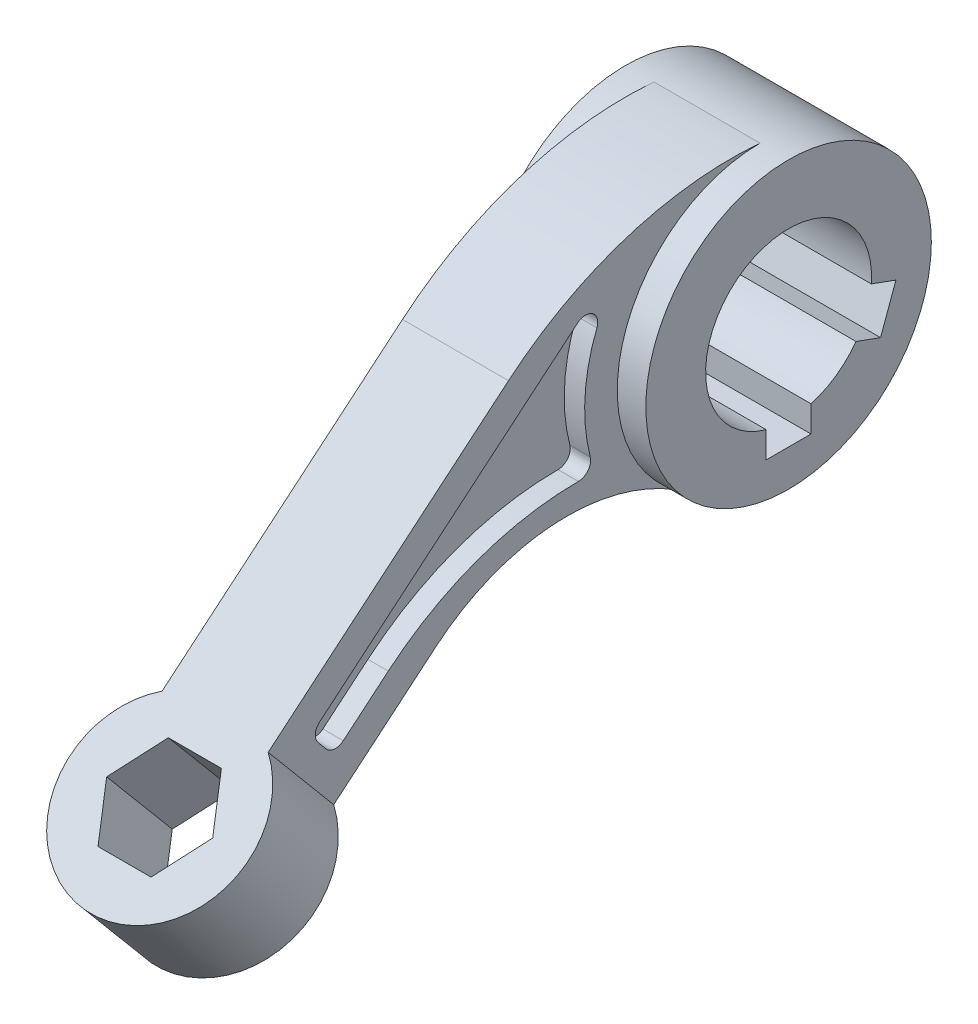
SolidWorks part; units mm, degrees
material "구리"
ref_plane "정면" through (0, 0, 0) normal (0, 0, 1) x (1, 0, 0)
ref_plane "윗면" through (0, 0, 0) normal (0, 1, 0) x (1, 0, 0)
ref_plane "우측면" through (0, 0, 0) normal (1, 0, 0) x (0, 0, -1)
sketch "Sketch1" plane through (0, 0, 0) normal (1, 0, 0) x (0, 0, -1)
  line L0 (0, 2.5639) -> (0, -54.5639) construction
  line L1 (22.5509, -14.0608) -> (16.5175, -11.8648)
  line L2 (-5.5, -26) -> (5.5, -26)
  line L3 (-5.5, -26) -> (-5.5, -19.5794)
  line L5 (5.5, -26) -> (5.5, -19.5794)
  line L6 (22.5509, -14.0608) -> (26.3131, -3.7242)
  line L7 (26.3131, -3.7242) -> (20.2797, -1.5282)
  line L9 (-61.6651, 15.4048) -> (-134.1818, -45.4439)
  line L10 (-134.1818, -45.4439) -> (-118.1121, -64.595)
  line L11 (-118.1121, -64.595) -> (-79.5317, -32.2222)
  line L12 (53.4671, 35) -> (-107.5928, 35) construction
  line L13 (-44.6559, 19.234) -> (-107.9587, -33.8834)
  line L14 (-108.3284, -38.1099) -> (-106.4001, -40.408)
  line L15 (-102.1736, -40.7778) -> (-91.1413, -31.5206)
  circle A0 centre (0, 0) radius 35
  arc A1 (5.5, -19.5794) -> (16.5175, -11.8648) centre (0, 0) ccw
  arc A2 (20.2797, -1.5282) -> (-5.5, -19.5794) centre (0, 0) ccw
  arc A3 (-61.6651, 15.4048) -> (0, 35) centre (-7.0281, -49.7089) cw
  arc A4 (-79.5317, -32.2222) -> (-20.4496, -28.4045) centre (-47.3923, -70.5244) cw
  arc A5 (-44.6559, 19.234) -> (-41.9077, 19.7514) centre (-42.7902, 16.8815) cw
  arc A6 (-91.1413, -31.5206) -> (-44.5255, -14.5531) centre (-44.5236, -87.0775) cw
  arc A7 (-39.9988, 15.7828) -> (-41.6217, -10.7997) centre (0, 0) ccw
  arc A8 (-41.9077, 19.7514) -> (-39.9988, 15.7828) centre (-42.7894, 16.8839) cw
  circle A10 centre (0, 0) radius 43 construction
  arc A11 (-41.6217, -10.7997) -> (-44.5255, -14.5531) centre (-44.5256, -11.5531) cw
  arc A13 (-108.3284, -38.1099) -> (-107.9587, -33.8834) centre (-106.0303, -36.1815) cw
  arc A14 (-106.4001, -40.408) -> (-102.1736, -40.7778) centre (-104.1019, -38.4796) ccw
  point P10 (0, -26)
  point P18 (0, 0)
  point P27 (-77.3476, -32.9486)
  point P28 (-18.8777, -29.4726)
  point P29 (-72.5951, -35.2385)
  point P32 (-17.1176, -30.5285)
  point P47 (-55.7741, 15.1214)
  point P48 (-55.5991, 15.1192)
  point P49 (-77.3351, -33.6863)
  point P50 (-76.8381, -33.996)
  point P51 (-56.5477, 15.1353)
  point P52 (0, 0)
  point P53 (0, 0)
  point P54 (-25.3958, -24.0843)
  point P55 (-20.0803, -28.8655)
  point P56 (0, 0)
  point P57 (0, 0)
  point P58 (-56.5002, 15.1342)
  point P59 (-56.2237, 15.1286)
  point P60 (0, 0)
  point P61 (0, 0)
  point P62 (-76.1089, -35.3273)
  point P63 (-74.944, -23.6864)
  point P64 (-47.1735, 19.4204)
  point P65 (-42.3042, -7.7043)
  point P66 (0, 0)
  point P67 (-41.6995, -9.5962)
  point P68 (-58.1212, 10.0015)
  point P69 (-53.0013, 12.3908)
  point P70 (-52.148, 12.3908)
  point P71 (0, 0)
  point P72 (-53.78, 13.7275)
  point P73 (-44.8926, 18.2271)
  point P74 (-45.1452, 16.2681)
  point P75 (-47.3347, 15.2705)
  point P76 (-46.1151, 14.3784)
  point P77 (-46.4038, 15.2444)
  point P78 (-102.1244, -36.128)
  point P79 (0, 0)
  point P80 (-44.6502, -14.0608)
  point P81 (-41.1655, -12.3445)
  point P82 (-44.8286, -13.315)
  point P83 (-48.6463, 12.4997)
  point P84 (-46.7209, 11.9654)
  point P85 (-62.2818, 16.3995)
  point P86 (0, 0)
  point P87 (-40.699, 10.6159)
  point P88 (-41.6079, -11.1231)
  point P89 (-73.3179, -34.9335)
  point P90 (-19.5792, -29.0113)
  point P91 (-60.2686, 15.0325)
  point P92 (-23.1853, -26)
  point P93 (0, 0)
  point P94 (-44.3341, -15.2674)
  point P95 (-41.1562, -10.5605)
  point P96 (-46.8563, 15.815)
  point P97 (0, 0)
  point P98 (-58.0521, 15.2005)
  point P99 (-41.9563, 9.4166)
  point P100 (-61.6651, 15.7828)
  point P101 (-44.6504, -14.0608)
  point P102 (0, 0)
  point P103 (0, 0)
  point P104 (-20.4496, -28.4045)
  point P105 (0, 0)
  point P106 (0, 0)
  point P107 (-44.5256, -14.5531)
  dimension "D1" = 70
  dimension "D5" = 85
  dimension "D7" = 50
  dimension "D12" = 3
  dimension "D14" = 8
  dimension "D15" = 3
  dimension "D16" = 3
  dimension "D17" = 3
  dimension "D2" = 26
  dimension "D3" = 11
  dimension "D6" = 25
  dimension "D8" = 40
  dimension "D9" = 132
  dimension "D13" = 8
  dimension "D11" = 8
  dimension "D4" = 2
extrude "Boss-Extrude2" add sketch "Sketch1" along normal mid plane 26 contours L11 A4 A0 A3 L9 L10 A14 L14 A13 L13 A5 A8 A7 A11 A6 L15 region at (0, 29.7052, 32.2634)
extrude "Boss-Extrude3" add sketch "Sketch1<4>" along normal mid plane 40 contours A3 A0 A2 L7 L6 L1 A1 L5 L2 L3 region at (0, 24.0487, -24.0487)
sketch "Sketch1<4>" plane through (0, 0, 0) normal (1, 0, 0) x (0, 0, -1) same geometry as "Sketch1"
extrude "Boss-Extrude4" add sketch "Sketch1<5>" along normal mid plane 16 contours L14 A14 L15 A6 A11 A7 A8 A5 L13 A13 region at (0, -10.3925, 67.4893)
sketch "Sketch1<5>" plane through (0, 0, 0) normal (1, 0, 0) x (0, 0, -1) same geometry as "Sketch1"
ref_plane "Plane1" through (0, 29.8285, 25.0291) normal (0, -0.766, -0.6428) x (-1, 0, 0)
sketch "Sketch2" plane through (0, 29.8285, 25.0291) normal (0, -0.766, -0.6428) x (-1, 0, 0)
  line L0 (-13, -132) -> (13, -132) construction
  line L2 (6.5, -120.7417) -> (-6.5, -120.7417)
  line L3 (-6.5, -120.7417) -> (-13, -132)
  line L4 (-13, -132) -> (-6.5, -143.2583)
  line L5 (-6.5, -143.2583) -> (6.5, -143.2583)
  line L6 (6.5, -143.2583) -> (13, -132)
  line L7 (13, -132) -> (6.5, -120.7417)
  circle A0 centre (0, -132) radius 22
  circle A1 centre (0, -132) radius 11.2583 construction
  point P4 (0, 0)
  dimension "D1" = 44
  dimension "D2" = 13
extrude "Boss-Extrude5" add sketch "Sketch2" along normal mid plane 25
extrude "Cut-Extrude1" cut sketch "Sketch2<2>" against normal mid plane 25 contours L6 L7 L2 L3 L4 L5 region at (0, -55.0195, 126.1469)
sketch "Sketch2<2>" plane through (0, 29.8285, 25.0291) normal (0, -0.766, -0.6428) x (-1, 0, 0) same geometry as "Sketch2"
